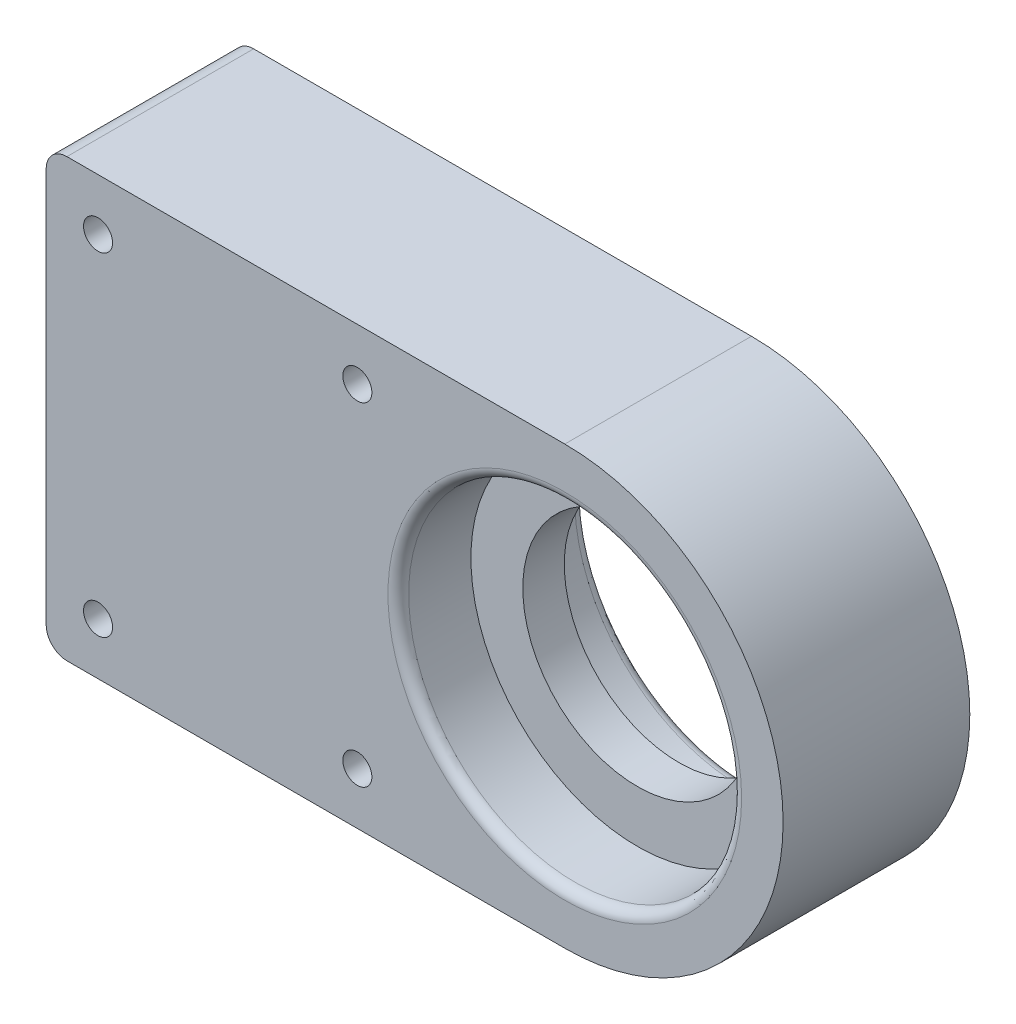
SolidWorks part; units mm, degrees
ref_plane "Front Plane" through (0, 0, 0) normal (0, 0, 1) x (1, 0, 0)
ref_plane "Top Plane" through (0, 0, 0) normal (0, 1, 0) x (1, 0, 0)
ref_plane "Right Plane" through (0, 0, 0) normal (1, 0, 0) x (0, 0, -1)
sketch "Sketch1" plane through (0, 0, 0) normal (0, 0, 1) x (1, 0, 0)
  line L0 (0, 21.05) -> (-50, 21.05)
  line L1 (-50, 21.05) -> (-50, -21.05)
  line L2 (-50, -21.05) -> (0, -21.05)
  circle A0 centre (0, 0) radius 16.05
  arc A1 (0, -21.05) -> (0, 21.05) centre (0, 0) ccw
  dimension "D1" = 32.1
  dimension "D2" = 5
  dimension "D3" = 50
extrude "Boss-Extrude1" add sketch "Sketch1" along normal blind 9 and the other way blind 9
sketch "Sketch2" plane through (0, 0, 0) normal (0, 0, -1) x (-1, 0, 0)
  line L3 (0, -21.05) -> (50, -21.05)
  line L4 (50, -21.05) -> (50, 21.05)
  line L5 (50, 21.05) -> (0, 21.05)
  line L6 (0, -21.05) -> (50, -21.05)
  line L7 (50, -21.05) -> (50, 21.05)
  line L8 (50, 21.05) -> (0, 21.05)
  circle A0 centre (0, 0) radius 11.05
  arc A1 (0, 21.05) -> (0, -21.05) centre (0, 0) ccw
  arc A2 (0, 21.05) -> (0, -21.05) centre (0, 0) ccw
  circle A3 centre (0, 0) radius 16.05 construction
  dimension "D2" = 5
  dimension "D1" = 0
extrude "Boss-Extrude2" add sketch "Sketch2" against normal offset from surface 7 and the other way offset from surface 7 up to face at (-19.7375, 0, 9) other way up to face at (16.05, 0, -9)
sketch "Sketch3" plane through (0, 0, 9) normal (0, 0, 1) x (1, 0, 0)
  line L0 (0, 21.05) -> (-50, 21.05) construction
  line L1 (-45, 16.05) -> (-20, 16.05) construction
  line L2 (-45, 16.05) -> (-45, -16.05) construction
  line L3 (-45, -16.05) -> (-20, -16.05) construction
  line L4 (-20, 16.05) -> (-20, -16.05) construction
  line L5 (-50, 21.05) -> (-50, -21.05) construction
  line L6 (-50, -21.05) -> (0, -21.05) construction
  circle A0 centre (-45, 16.05) radius 1.4
  circle A1 centre (-20, 16.05) radius 1.4
  circle A2 centre (-20, -16.05) radius 1.4
  circle A3 centre (-45, -16.05) radius 1.4
  dimension "D1" = 5
  dimension "D2" = 5
  dimension "D3" = 5
  dimension "D4" = 25
extrude "Cut-Extrude1" cut sketch "Sketch3" against normal through all
fillet "Fillet1" radius 2 2 edges at (-50, -21.05, 0) (-50, 21.05, 0)
fillet "Fillet2" radius 1 2 edges at (16.05, 0, -9) (16.05, 0, 9)
